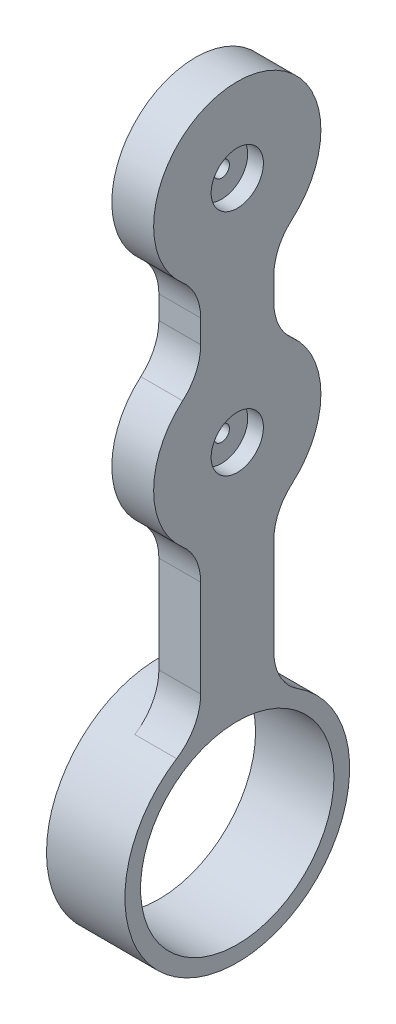
SolidWorks part; units mm, degrees
other "Markup1"
sketch "Sketch6" plane through (4, -129.991, 21.5) normal (0.5166, -0.3109, 0.7978) x (0.8561, 0.2021, -0.4756)
ref_plane "Front Plane" through (0, 0, 0) normal (0, 0, 1) x (1, 0, 0)
ref_plane "Top Plane" through (0, 0, 0) normal (0, 1, 0) x (1, 0, 0)
ref_plane "Right Plane" through (0, 0, 0) normal (1, 0, 0) x (0, 0, -1)
sketch "Sketch1" plane through (0, 0, 0) normal (1, 0, 0) x (0, 0, -1)
  line L0 (0, -108.491) -> (0, 108.491) construction
  line L1 (-70.7847, 0) -> (70.7847, 0) construction
  line L2 (-7, -14.3875) -> (-7, -29.3875)
  line L3 (-7, -58.1625) -> (-7, -88.1625)
  line L4 (7, -58.1625) -> (7, -88.1625)
  line L5 (7, -14.3875) -> (7, -29.3875)
  circle A0 centre (0, 0) radius 5
  arc A1 (7, -14.3875) -> (-7, -14.3875) centre (0, 0) ccw
  circle A2 centre (0, -43.775) radius 5
  arc A3 (-7, -29.3875) -> (-7, -58.1625) centre (0, -43.775) ccw
  arc A4 (-7, -88.1625) -> (7, -88.1625) centre (0, -108.491) ccw
  circle A5 centre (0, -108.491) radius 18.5
  arc A6 (7, -58.1625) -> (7, -29.3875) centre (0, -43.775) ccw
  point P4 (0, 0)
  point P8 (0, 0)
  dimension "D1" = 10
  dimension "D2" = 32
  dimension "D3" = 10
  dimension "D4" = 32
  dimension "D5" = 43
  dimension "D6" = 37
  dimension "D7" = 7
  dimension "D8" = 15
  dimension "D9" = 30
extrude "Boss-Extrude1" add sketch "Sketch1" along normal blind 4 and the other way blind 4 contours L3 A4 L4 A6 L5 A1 L2 A3
fillet "Fillet1" radius 10 8 edges at (0, -58.1625, 7) (0, -88.1625, 7) (0, -88.1625, -7) (0, -58.1625, -7) (0, -29.3875, -7) (0, -29.3875, 7) (0, -14.3875, 7) (0, -14.3875, -7)
sketch "Sketch2" plane through (4, 0, 0) normal (1, 0, 0) x (0, 0, -1)
  circle A0 centre (0, 0) radius 5
  arc A1 (-10.4615, -31.6689) -> (-10.4615, -55.881) centre (0, -43.775) ccw construction
  arc A2 (-10.4615, -31.6689) -> (-10.4615, -55.881) centre (0, -43.775) ccw construction
  circle A3 centre (0, -43.775) radius 5
  dimension "D1" = 10
  dimension "D2" = 10
extrude "Cut-Extrude1" cut sketch "Sketch2" against normal blind 3
sketch "Sketch3" plane through (1, 0, 0) normal (1, 0, 0) x (0, 0, -1)
  circle A0 centre (0, 0) radius 1.5
  circle A1 centre (0, -43.775) radius 5 construction
  circle A2 centre (0, -43.775) radius 5 construction
  circle A3 centre (0, -43.775) radius 1.5
  dimension "D1" = 3
  dimension "D2" = 3
extrude "Cut-Extrude2" cut sketch "Sketch3" against normal up to surface (5 mm away) up to face at (-4, -48.1499, 0)
sketch "Sketch4" plane through (4, 0, 0) normal (1, 0, 0) x (0, 0, -1)
  circle A0 centre (0, -108.491) radius 18.5
  arc A1 (-11.6032, -90.3909) -> (11.6032, -90.3909) centre (0, -108.491) ccw construction
  arc A2 (-11.6032, -90.3909) -> (11.6032, -90.3909) centre (0, -108.491) ccw
  dimension "D1" = 37
extrude "Cut-Extrude3" cut sketch "Sketch4" against normal up to surface (8 mm away) contours A0 up to face at (-4, 0, -1.5)
sketch "Sketch5" plane through (-4, 0, 0) normal (-1, 0, 0) x (0, 0, 1)
  circle A0 centre (0, -108.491) radius 18.5 construction
  circle A1 centre (0, -108.491) radius 18.5
  arc A2 (-11.6032, -90.3909) -> (11.6032, -90.3909) centre (0, -108.491) ccw construction
  arc A3 (-11.6032, -90.3909) -> (11.6032, -90.3909) centre (0, -108.491) ccw construction
  circle A4 centre (0, -108.491) radius 21.5
  circle M4 centre (0, -108.491) radius 18.5
extrude "Boss-Extrude2" add sketch "Sketch5" along normal blind 7 contours M4 | A4 region at (-4, -108.491, 0)
